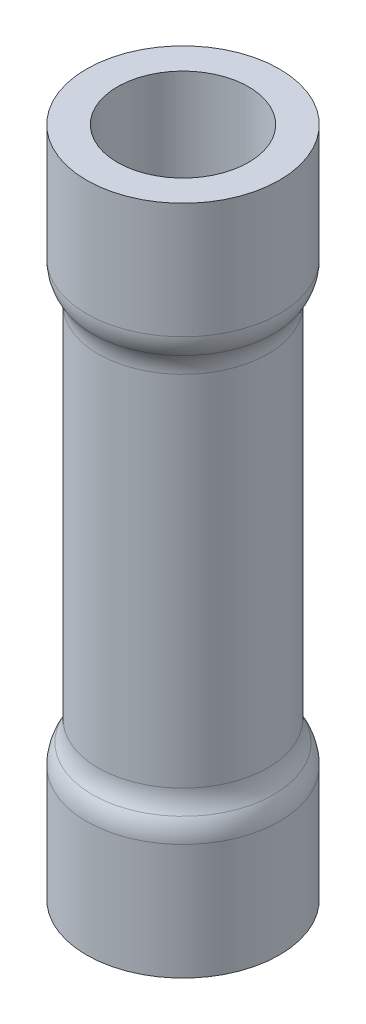
SolidWorks part; units mm, degrees
note: '?' marks a value the reader was unsure of.
material "PVC 0.007 Plasticized"
ref_plane "Front Plane" through (0, 0, 0) normal (0, 0, 1) x (1, 0, 0)
ref_plane "Top Plane" through (0, 0, 0) normal (0, 1, 0) x (1, 0, 0)
ref_plane "Right Plane" through (0, 0, 0) normal (1, 0, 0) x (0, 0, -1)
sketch "Sketch1" plane through (0, 0, 0) normal (0, 0, 1) x (1, 0, 0)
  line L0 (2.794, 16.95) -> (2.794, 5.148)
  line L1 (3.175, 0) -> (3.175, 3.81)
  line L2 (0, 11.049) -> (3.175, 11.049) construction
  line L3 (3.175, 18.288) -> (3.175, 22.098)
  line L5 (0, 22.098) -> (0, 0) construction
  arc A0 (3.175, 3.81) -> (2.9845, 4.479) centre (1.905, 3.81) ccw
  arc A1 (2.9845, 4.479) -> (2.794, 5.148) centre (4.064, 5.148) cw
  arc A2 (3.175, 18.288) -> (2.9845, 17.619) centre (1.905, 18.288) cw
  arc A3 (2.9845, 17.619) -> (2.794, 16.95) centre (4.064, 16.95) ccw
  dimension "D5" = 1.27
  dimension "D1" = 22.098
  dimension "D2" = 3.175
  dimension "D3" = 0.381
  dimension "D4" = 3.81
revolve "Revolve-Thin1" add sketch "Sketch1" angle 360 about L5
other "CPoint1" parameters "Diameter"=4.572, "StubLength"=12.7
ref_axis "Axis1" through (0, 32.098, 0) along (0, -1, 0)?
